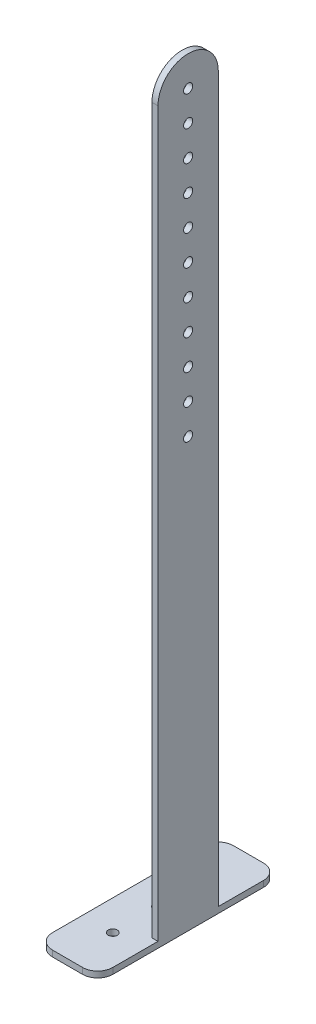
SolidWorks part; units mm, degrees
ref_plane "前视基准面" through (0, 0, 0) normal (0, 0, 1) x (1, 0, 0)
ref_plane "上视基准面" through (0, 0, 0) normal (0, 1, 0) x (1, 0, 0)
ref_plane "右视基准面" through (0, 0, 0) normal (1, 0, 0) x (0, 0, -1)
sketch "草图1" plane through (0, 0, 0) normal (0, 0, 1) x (1, 0, 0)
  line L0 (0, 0) -> (0, 250)
  line L1 (0, 250) -> (2, 250)
  line L2 (2, 250) -> (2, 0)
  line L3 (2, 0) -> (0, 0)
extrude "凸台-拉伸1" add sketch "草图1" along normal blind 20
sketch "草图2" plane through (0, 0, 0) normal (0, 0, -1) x (-1, 0, 0)
  line L0 (-2, 0) -> (-2, -2)
  line L1 (-2, -2) -> (18, -2)
  line L2 (18, -2) -> (18, 0)
  line L3 (18, 0) -> (-2, 0)
extrude "凸台-拉伸2" add sketch "草图2" along normal blind 20 and the other way blind 40
sketch "草图3" plane through (0, 0, 0) normal (0, 1, 0) x (1, 0, 0)
  line L0 (-18, -10) -> (-8, -10) construction
  line L1 (-8, -10) -> (-8, -25) construction
  line L8 (0, -20) -> (0, 0)
  line L9 (0, 0) -> (2, 0)
  line L10 (2, 0) -> (2, 20)
  line L11 (2, 20) -> (-18, 20)
  line L12 (-18, 20) -> (-18, -40)
  line L13 (-18, -40) -> (2, -40)
  line L14 (2, -40) -> (2, -20)
  line L15 (2, -20) -> (0, -20)
  line L16 (0, -20) -> (0, 0) construction
  line L17 (0, 0) -> (2, 0) construction
  line L18 (2, 0) -> (2, 20) construction
  line L19 (2, 20) -> (-18, 20) construction
  line L20 (-18, 20) -> (-18, -40) construction
  line L21 (-18, -40) -> (2, -40) construction
  line L22 (2, -40) -> (2, -20) construction
  line L23 (2, -20) -> (0, -20) construction
  circle A0 centre (-8, -25) radius 1.51
  circle A1 centre (-8, -10) radius 1.51
  circle A2 centre (-8, 5) radius 1.51
  dimension "D1" = 0
extrude "切除-拉伸1" cut sketch "草图3" against normal through all
fillet "圆角1" radius 5 4 edges at (2, -1, -20) (-18, -1, -20) (2, -1, 40) (-18, -1, 40)
fillet "圆角2" 2 edges at (1, 250, 0) (1, 250, 20) type full round first side face at (1, 125, 0) second side face at (1, 125, 20) middle face at (1, 250, 10)
sketch "草图4" plane through (0, 0, 0) normal (-1, 0, 0) x (0, 0, 1)
  line L3 (20, 0) -> (20, 240)
  line L4 (0, 240) -> (0, 0)
  line L5 (0, 0) -> (20, 0)
  line L6 (20, 0) -> (20, 240) construction
  line L7 (0, 240) -> (0, 0) construction
  line L8 (0, 0) -> (20, 0) construction
  circle A0 centre (10, 240) radius 1.51
  arc A1 (20, 240) -> (0, 240) centre (10, 240) ccw
  arc A2 (20, 240) -> (0, 240) centre (10, 240) ccw construction
  circle A3 centre (10, 230) radius 1.51
  circle A4 centre (10, 220) radius 1.51
  circle A5 centre (10, 210) radius 1.51
  circle A6 centre (10, 200) radius 1.51
  circle A7 centre (10, 190) radius 1.51
  circle A8 centre (10, 180) radius 1.51
  circle A9 centre (10, 170) radius 1.51
  circle A10 centre (10, 160) radius 1.51
  circle A11 centre (10, 150) radius 1.51
  circle A12 centre (10, 140) radius 1.51
  dimension "D2" = 11
  dimension "D1" = 0
extrude "切除-拉伸2" cut sketch "草图4" against normal through all
